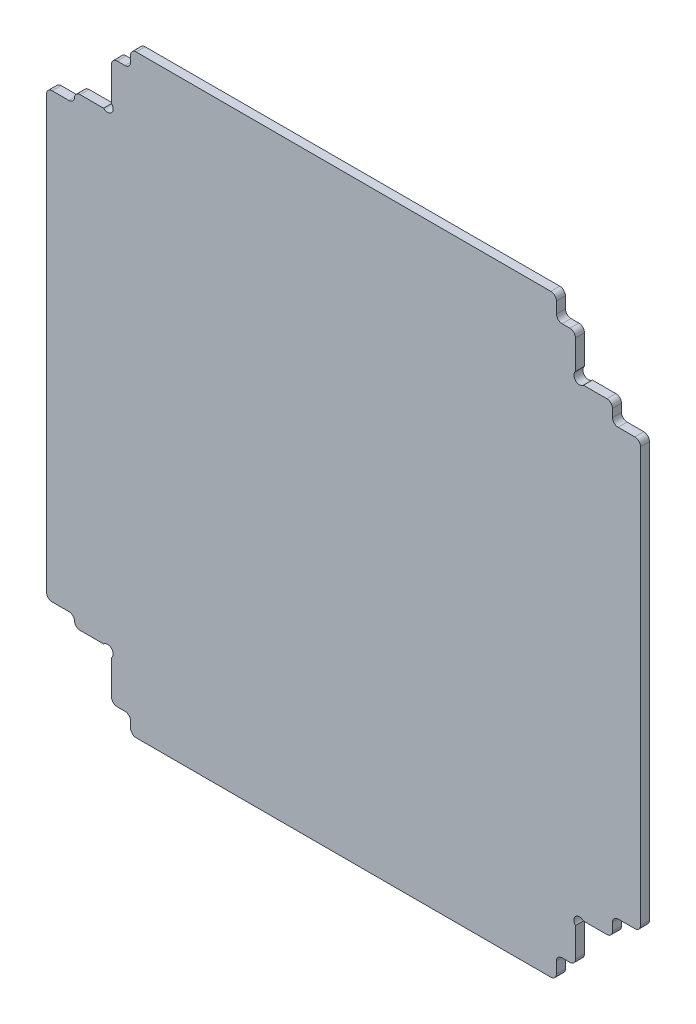
SolidWorks part; units mm, degrees
ref_plane "Front Plane" through (0, 0, 0) normal (0, 0, 1) x (1, 0, 0)
ref_plane "Top Plane" through (0, 0, 0) normal (0, 1, 0) x (1, 0, 0)
ref_plane "Right Plane" through (0, 0, 0) normal (1, 0, 0) x (0, 0, -1)
sketch "Sketch1" plane through (0, 0, 0) normal (0, 0, 1) x (1, 0, 0)
  line L0 (53, 53) -> (-53, -53) construction
  line L1 (53, 53) -> (-53, 53)
  line L2 (53, 53) -> (53, -53)
  line L3 (53, -53) -> (-53, -53)
  line L4 (-53, 53) -> (-53, -53)
  point P4 (0, 0)
  dimension "D1" = 106
  dimension "D2" = 106
extrude "mainOutline" add sketch "Sketch1" along normal blind 1.6
sketch "axisLabels" plane through (0, 0, 0) normal (0, 0, -1) x (-1, 0, 0)
  text T0 "+Y"
  text T1 "+X"
sketch "Sketch4" plane through (0, 0, 0) normal (0, 0, -1) x (-1, 0, 0)
  line L1 (-41.4, -41.4) -> (-48, -41.4)
  line L3 (-41.4, -49) -> (-41.4, -41.4)
  line L5 (-60.1065, -39) -> (-49.9975, -39)
  line L7 (-39, -61.4521) -> (-39, -49.9)
  line L9 (39, -56.2753) -> (39, -49.9)
  line L10 (-53, 53) -> (53, 53) construction
  line L11 (41.4, -49.9) -> (41.4, -41.4)
  line L12 (-53, -53) -> (-53, 53) construction
  line L13 (41.4, -41.4) -> (48, -41.4)
  line L15 (48, -40.5) -> (55.5177, -40.5)
  line L17 (55.3838, 40.5) -> (48, 40.5)
  line L19 (39, 57.6877) -> (39, 49.9)
  line L21 (-39, 59.8804) -> (-39, 49.9)
  line L23 (-56.8428, 39) -> (-49.9975, 39)
  line L25 (-41.4, 41.4) -> (-41.4, 49)
  line L27 (-48, 41.4) -> (-41.4, 41.4)
  line L29 (41.4, 49.9) -> (41.4, 41.4)
  line L31 (48, 41.4) -> (41.4, 41.4)
  line L32 (-48, 41.4) -> (-48, 39)
  line L33 (-48, 39) -> (-49.9975, 39)
  line L34 (-41.4, 49) -> (-39, 49)
  line L35 (-39, 49) -> (-39, 49.9)
  line L36 (48, 40.5) -> (48, 41.4)
  line L37 (39, 49.9) -> (41.4, 49.9)
  line L38 (48, -40.5) -> (48, -41.4)
  line L39 (39, -49.9) -> (41.4, -49.9)
  line L40 (-41.4, -49) -> (-39, -49)
  line L41 (-39, -49) -> (-39, -49.9)
  line L42 (-49.9975, -39) -> (-48, -39)
  line L43 (-48, -39) -> (-48, -41.4)
  line L44 (-39, 59.8804) -> (-56.8428, 59.8804)
  line L45 (-56.8428, 59.8804) -> (-56.8428, 39)
  line L46 (53, 53) -> (53, -53) construction
  line L47 (-60.1065, -39) -> (-60.1065, -61.4521)
  line L48 (-60.1065, -61.4521) -> (-39, -61.4521)
  line L49 (39, -56.2753) -> (55.5177, -56.2753)
  line L50 (55.5177, -56.2753) -> (55.5177, -40.5)
  line L51 (55.3838, 40.5) -> (55.3838, 57.6877)
  line L52 (55.3838, 57.6877) -> (39, 57.6877)
  line L53 (53, -53) -> (-53, -53) construction
  dimension "D1" = 14
  dimension "D2" = 11.6
  dimension "D3" = 5
  dimension "D4" = 12.5
  dimension "D5" = 11.6
  dimension "D6" = 3.1
  dimension "D7" = 12.5
  dimension "D8" = 14
  dimension "D9" = 3.1
  dimension "D10" = 5
  dimension "D11" = 11.6
  dimension "D12" = 11.6
  dimension "D13" = 14
  dimension "D14" = 14
  dimension "D15" = 11.6
  dimension "D16" = 11.6
  dimension "D17" = 5
  dimension "D18" = 4
  dimension "D19" = 14
  dimension "D20" = 14
  dimension "D21" = 11.6
  dimension "D22" = 11.6
  dimension "D23" = 4
  dimension "D24" = 5
extrude "railCutouts" cut sketch "Sketch4" against normal through all
sketch "Sketch5" plane through (0, 0, 0) normal (0, 0, -1) x (-1, 0, 0)
  line L0 (-48.7071, -39.7071) -> (-52.4015, -43.4015) construction
  line L1 (-48, -40.4142) -> (-51.6944, -44.1086) construction
  line L2 (-49.4142, -39) -> (-53.1086, -42.6944) construction
  line L3 (-48, -41.4) -> (-48, -39) construction
  line L4 (-48, 39) -> (-48, 41.4) construction
  line L5 (-42.1071, -42.1071) -> (-45.4445, -45.4445) construction
  line L6 (-41.4, -42.8142) -> (-44.7374, -46.1516)
  line L7 (-42.8142, -41.4) -> (-46.1516, -44.7374)
  line L8 (-39.7071, -49.7071) -> (-42.6199, -52.6199) construction
  line L9 (-39, -50.4142) -> (-41.9128, -53.327) construction
  line L10 (-40.4142, -49) -> (-43.327, -51.9128) construction
  line L11 (39.7071, -50.6071) -> (41.4231, -52.3231) construction
  line L12 (40.4142, -49.9) -> (42.1302, -51.616) construction
  line L13 (39, -51.3142) -> (40.716, -53.0302) construction
  line L14 (42.1071, -42.1071) -> (44.0402, -44.0402) construction
  line L15 (42.8142, -41.4) -> (44.7473, -43.3331)
  line L16 (41.4, -42.8142) -> (43.3331, -44.7473)
  line L17 (48.7071, -41.2071) -> (49.9793, -42.4793) construction
  line L18 (49.4142, -40.5) -> (50.6865, -41.7722) construction
  line L19 (48, -41.9142) -> (49.2722, -43.1865) construction
  line L20 (48.7071, 41.2071) -> (50.5001, 43.0001) construction
  line L21 (48, 41.9142) -> (49.793, 43.7072) construction
  line L22 (49.4142, 40.5) -> (51.2072, 42.293) construction
  line L23 (42.1071, 42.1071) -> (44.029, 44.029) construction
  line L24 (41.4, 42.8142) -> (43.3219, 44.7361)
  line L25 (42.8142, 41.4) -> (44.7361, 43.3219)
  line L26 (39.7071, 50.6071) -> (41.2638, 52.1638) construction
  line L27 (39, 51.3142) -> (40.5567, 52.8709) construction
  line L28 (40.4142, 49.9) -> (41.9709, 51.4567) construction
  line L29 (-48.7071, 39.7071) -> (-50.0606, 41.0606) construction
  line L30 (-49.4142, 39) -> (-50.7677, 40.3535) construction
  line L31 (-48, 40.4142) -> (-49.3535, 41.7677) construction
  line L32 (-42.1071, 42.1071) -> (-43.7968, 43.7968) construction
  line L33 (-42.8142, 41.4) -> (-44.5039, 43.0897)
  line L34 (-41.4, 42.8142) -> (-43.0897, 44.5039)
  line L35 (-39.7071, 49.7071) -> (-41.256, 51.256) construction
  line L36 (-40.4142, 49) -> (-41.9631, 50.5489) construction
  line L37 (-39, 50.4142) -> (-40.5489, 51.9631) construction
  line L38 (-41.4, 41.4) -> (-41.4, 49) construction
  line L39 (-39, 49) -> (-39, 53) construction
  line L40 (39, 53) -> (39, 49.9) construction
  line L41 (41.4, 49.9) -> (41.4, 41.4) construction
  line L42 (48, 41.4) -> (48, 40.5) construction
  line L43 (39, -49.9) -> (39, -53) construction
  line L44 (41.4, -41.4) -> (41.4, -49.9) construction
  line L45 (53, -40.5) -> (48, -40.5) construction
  line L46 (-39, -53) -> (-39, -49) construction
  line L47 (-41.4, -49) -> (-41.4, -41.4) construction
  arc A0 (-48, -40.4142) -> (-49.4142, -39) centre (-48.7071, -39.7071) ccw construction
  arc A1 (-53.1086, -42.6944) -> (-51.6944, -44.1086) centre (-52.4015, -43.4015) ccw construction
  arc A2 (-41.4, -42.8142) -> (-42.8142, -41.4) centre (-42.1071, -42.1071) ccw
  arc A3 (-46.1516, -44.7374) -> (-44.7374, -46.1516) centre (-45.4445, -45.4445) ccw
  arc A4 (-39, -50.4142) -> (-40.4142, -49) centre (-39.7071, -49.7071) ccw construction
  arc A5 (-43.327, -51.9128) -> (-41.9128, -53.327) centre (-42.6199, -52.6199) ccw construction
  arc A6 (40.4142, -49.9) -> (39, -51.3142) centre (39.7071, -50.6071) ccw construction
  arc A7 (40.716, -53.0302) -> (42.1302, -51.616) centre (41.4231, -52.3231) ccw construction
  arc A8 (42.8142, -41.4) -> (41.4, -42.8142) centre (42.1071, -42.1071) ccw
  arc A9 (43.3331, -44.7473) -> (44.7473, -43.3331) centre (44.0402, -44.0402) ccw
  arc A10 (49.4142, -40.5) -> (48, -41.9142) centre (48.7071, -41.2071) ccw construction
  arc A11 (49.2722, -43.1865) -> (50.6865, -41.7722) centre (49.9793, -42.4793) ccw construction
  arc A12 (48, 41.9142) -> (49.4142, 40.5) centre (48.7071, 41.2071) ccw construction
  arc A13 (51.2072, 42.293) -> (49.793, 43.7072) centre (50.5001, 43.0001) ccw construction
  arc A14 (41.4, 42.8142) -> (42.8142, 41.4) centre (42.1071, 42.1071) ccw
  arc A15 (44.7361, 43.3219) -> (43.3219, 44.7361) centre (44.029, 44.029) ccw
  arc A16 (39, 51.3142) -> (40.4142, 49.9) centre (39.7071, 50.6071) ccw construction
  arc A17 (41.9709, 51.4567) -> (40.5567, 52.8709) centre (41.2638, 52.1638) ccw construction
  arc A18 (-49.4142, 39) -> (-48, 40.4142) centre (-48.7071, 39.7071) ccw construction
  arc A19 (-49.3535, 41.7677) -> (-50.7677, 40.3535) centre (-50.0606, 41.0606) ccw construction
  arc A20 (-42.8142, 41.4) -> (-41.4, 42.8142) centre (-42.1071, 42.1071) ccw
  arc A21 (-43.0897, 44.5039) -> (-44.5039, 43.0897) centre (-43.7968, 43.7968) ccw
  arc A22 (-40.4142, 49) -> (-39, 50.4142) centre (-39.7071, 49.7071) ccw construction
  arc A23 (-40.5489, 51.9631) -> (-41.9631, 50.5489) centre (-41.256, 51.256) ccw construction
  point P2 (-50.5543, -41.5543)
  point P9 (-43.7758, -43.7758)
  point P17 (-41.1635, -51.1635)
  point P24 (40.5651, -51.4651)
  point P31 (43.0736, -43.0736)
  point P38 (49.3432, -41.8432)
  point P45 (49.6036, 42.1036)
  point P52 (43.0681, 43.0681)
  point P59 (40.4855, 51.3855)
  point P66 (-49.3839, 40.3839)
  point P73 (-42.952, 42.952)
  point P80 (-40.4815, 50.4815)
  dimension "D2" = 1
  dimension "D1" = 45
  dimension "D3" = 45
  dimension "D4" = 45
  dimension "D5" = 45
  dimension "D6" = 45
  dimension "D7" = 45
  dimension "D8" = 45
  dimension "D9" = 45
  dimension "D10" = 45
  dimension "D11" = 45
  dimension "D12" = 45
  dimension "D13" = 45
extrude "dogbones" cut sketch "Sketch5" against normal through all
sketch "Sketch6" plane through (0, 0, 0) normal (0, 0, -1) x (-1, 0, 0)
  line L0 (-39, 50) -> (-39, 53) construction
  line L1 (-39, 49) -> (-39, 53) construction
  line L2 (-39, 53) -> (39, 53) construction
  line L3 (-40, 50) -> (-40, 53)
  line L4 (-38, 50) -> (-38, 53)
  line L5 (-49, 39) -> (-53, 39) construction
  line L6 (-53, 39) -> (-48, 39) construction
  line L7 (-49, 38) -> (-53, 38)
  line L8 (-49, 40) -> (-53, 40)
  line L9 (-49, -39) -> (-55.2142, -39) construction
  line L10 (-48, -39) -> (-53, -39) construction
  line L11 (-49, -40) -> (-55.2142, -40)
  line L12 (-49, -38) -> (-55.2142, -38)
  line L13 (-39, -50) -> (-39, -53.9161) construction
  line L14 (-39, -53) -> (-39, -49) construction
  line L15 (-38, -50) -> (-38, -53.9161)
  line L16 (-40, -50) -> (-40, -53.9161)
  line L17 (39, -50.9) -> (39, -54.538) construction
  line L18 (39, -49.9) -> (39, -53) construction
  line L19 (40, -50.9) -> (40, -54.538)
  line L20 (38, -50.9) -> (38, -54.538)
  line L21 (49, -40.5) -> (54.2026, -40.5) construction
  line L22 (53, -40.5) -> (48, -40.5) construction
  line L23 (49, -39.5) -> (54.2026, -39.5)
  line L24 (49, -41.5) -> (54.2026, -41.5)
  line L25 (49, 40.5) -> (54.5566, 40.5) construction
  line L26 (48, 40.5) -> (53, 40.5) construction
  line L27 (49, 41.5) -> (54.5566, 41.5)
  line L28 (49, 39.5) -> (54.5566, 39.5)
  line L29 (39, 50.9) -> (39, 55.8281) construction
  line L30 (39, 53) -> (39, 49.9) construction
  line L31 (38, 50.9) -> (38, 55.8281)
  line L32 (40, 50.9) -> (40, 55.8281)
  line L33 (-48, -41.4) -> (-48, -39) construction
  line L34 (-39, -49) -> (-41.4, -49) construction
  line L35 (41.4, -49.9) -> (39, -49.9) construction
  line L36 (48, -40.5) -> (48, -41.4) construction
  line L37 (48, 41.4) -> (48, 40.5) construction
  line L38 (39, 49.9) -> (41.4, 49.9) construction
  arc A0 (-40, 50) -> (-38, 50) centre (-39, 50) ccw
  arc A1 (-38, 53) -> (-40, 53) centre (-39, 53) ccw
  arc A2 (-49, 38) -> (-49, 40) centre (-49, 39) ccw
  arc A3 (-53, 40) -> (-53, 38) centre (-53, 39) ccw
  arc A4 (-49, -40) -> (-49, -38) centre (-49, -39) ccw
  arc A5 (-55.2142, -38) -> (-55.2142, -40) centre (-55.2142, -39) ccw
  arc A6 (-38, -50) -> (-40, -50) centre (-39, -50) ccw
  arc A7 (-40, -53.9161) -> (-38, -53.9161) centre (-39, -53.9161) ccw
  arc A8 (40, -50.9) -> (38, -50.9) centre (39, -50.9) ccw
  arc A9 (38, -54.538) -> (40, -54.538) centre (39, -54.538) ccw
  arc A10 (49, -39.5) -> (49, -41.5) centre (49, -40.5) ccw
  arc A11 (54.2026, -41.5) -> (54.2026, -39.5) centre (54.2026, -40.5) ccw
  arc A12 (49, 41.5) -> (49, 39.5) centre (49, 40.5) ccw
  arc A13 (54.5566, 39.5) -> (54.5566, 41.5) centre (54.5566, 40.5) ccw
  arc A14 (38, 50.9) -> (40, 50.9) centre (39, 50.9) ccw
  arc A15 (40, 55.8281) -> (38, 55.8281) centre (39, 55.8281) ccw
  point P6 (-39, 51.5)
  point P11 (-51, 39)
  point P21 (-52.1071, -39)
  point P30 (-39, -51.958)
  point P39 (39, -52.719)
  point P48 (51.6013, -40.5)
  point P57 (51.7783, 40.5)
  point P66 (39, 53.364)
  point P75 (-39, 49)
  dimension "D1" = 1
extrude "solarFillets" cut sketch "Sketch6" against normal through all
fillet "handlingFillets" radius 1 16 edges at (-41.4, -49.9, 0.8) (-38, -53, 0.8) (-53, -39.5, 0.8) (-48, -41.4, 0.8) (-48, 41.4, 0.8) (-53, 39.5, 0.8) (-41.4, 49.9, 0.8) (-38, 53, 0.8) (38, 53, 0.8) (41.4, 49, 0.8) (48, 41.4, 0.8) (53, 38, 0.8) (53, -38, 0.8) (48, -41.4, 0.8) (41.4, -49, 0.8) (38, -53, 0.8)
